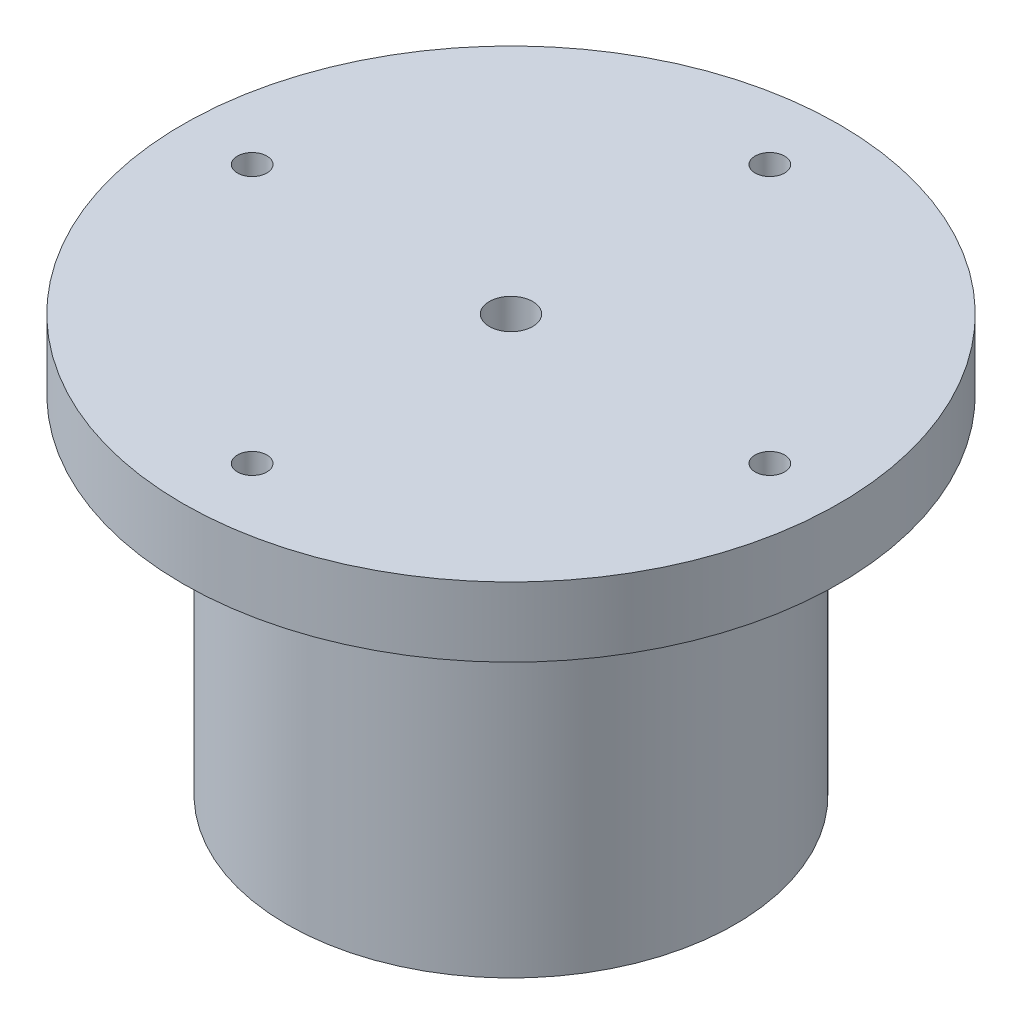
SolidWorks part; units mm, degrees
ref_plane "Front Plane" through (0, 0, 0) normal (0, 0, 1) x (1, 0, 0)
ref_plane "Top Plane" through (0, 0, 0) normal (0, 1, 0) x (1, 0, 0)
ref_plane "Right Plane" through (0, 0, 0) normal (1, 0, 0) x (0, 0, -1)
sketch "Sketch1" plane through (0, 0, 0) normal (0, 1, 0) x (1, 0, 0)
  circle A0 centre (0, 0) radius 17.825
  circle A1 centre (0, 0) radius 25.825
  dimension "D1" = 35.65
  dimension "D2" = 8
extrude "Boss-Extrude1" add sketch "Sketch1" along normal blind 40
sketch "Sketch2" plane through (0, 40, 0) normal (0, 1, 0) x (1, 0, 0)
  circle A0 centre (0, 0) radius 37.825
  circle A1 centre (0, 0) radius 25.825 construction
  dimension "D1" = 12
extrude "Boss-Extrude2" add sketch "Sketch2" along normal blind 8
sketch "Sketch3" plane through (0, 0, 0) normal (0, -1, 0) x (1, 0, 0)
  circle A0 centre (0, 0) radius 35.7791
extrude "Cut-Extrude1" [suppressed] cut sketch "Sketch3" against normal through all from offset 5 offset against normal yes
sketch "Sketch4" plane through (0, 40, 0) normal (0, -1, 0) x (1, 0, 0)
  line L0 (0, 0) -> (0, 37.825) construction
  circle A0 centre (0, 0) radius 37.825 construction
  circle A1 centre (0, 29.825) radius 1.7
  circle A2 centre (29.825, 0) radius 1.7
  circle A3 centre (0, -29.825) radius 1.7
  circle A4 centre (-29.825, 0) radius 1.7
  point P7 (28.0811, -4.4422)
  point P8 (0, 0)
  point P16 (0, 0)
  dimension "D1" = 8
  dimension "D2" = 3.4
  dimension "D3" = 4
extrude "Cut-Extrude2" cut sketch "Sketch4" against normal through all
sketch "Sketch5" plane through (0, 40, 0) normal (0, -1, 0) x (1, 0, 0)
  circle A0 centre (0, 29.825) radius 2.85
  circle A1 centre (29.825, 0) radius 2.85
  circle A2 centre (0, -29.825) radius 2.85
  circle A3 centre (-29.825, 0) radius 2.85
  point P3 (-48.3946, 2.4369)
  point P4 (0, 0)
  point P12 (0, 0)
  dimension "D1" = 5.7
  dimension "D2" = 4
extrude "Cut-Extrude3" cut sketch "Sketch5" against normal blind 4
fillet "Fillet1" radius 2 1 edges at (0, 0, 17.825)
sketch "Sketch6" plane through (0, 40, 0) normal (0, -1, 0) x (1, 0, 0)
  circle A0 centre (0, 0) radius 2.5
  dimension "D1" = 5
extrude "Cut-Extrude4" cut sketch "Sketch6" against normal through all
